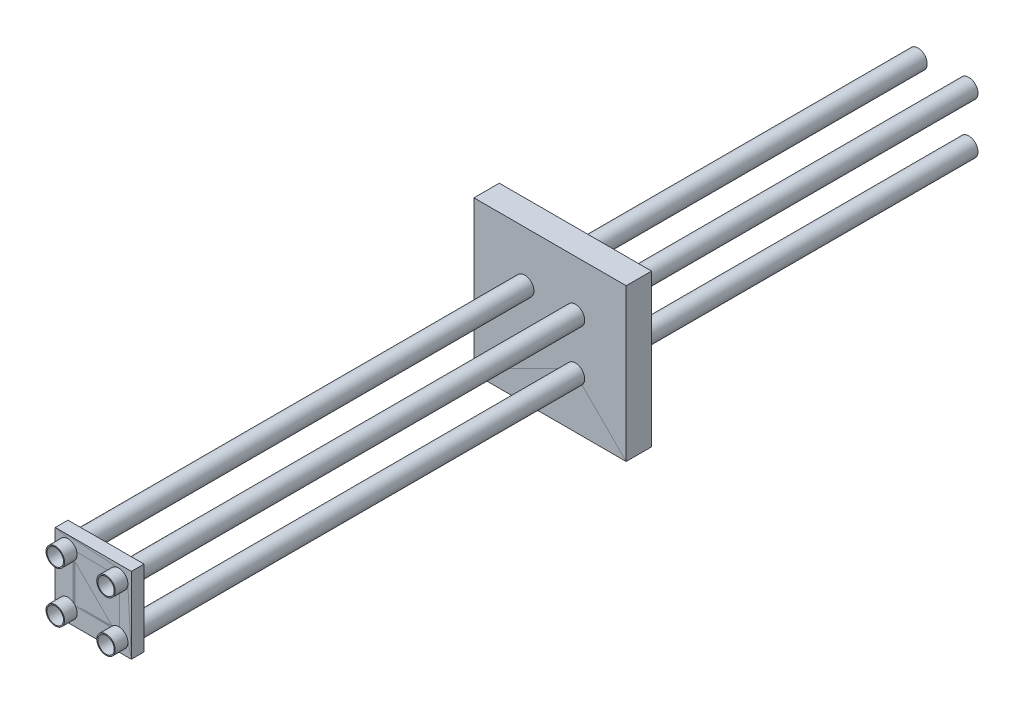
SolidWorks part; units mm, degrees
note: The reader was unsure of these and kept them because the rebuilt part matched: shared geometry of "Sketch7<2>".
ref_plane "Front Plane" through (0, 0, 0) normal (0, 0, 1) x (1, 0, 0)
ref_plane "Top Plane" through (0, 0, 0) normal (0, 1, 0) x (1, 0, 0)
ref_plane "Right Plane" through (0, 0, 0) normal (1, 0, 0) x (0, 0, -1)
sketch "Sketch1" plane through (0, 0, 0) normal (0, 0, 1) x (1, 0, 0)
  line L1 (-1500, 1500) -> (1500, 1500)
  line L2 (-1500, 1500) -> (-1500, -1500)
  line L3 (-1500, -1500) -> (1500, -1500)
  line L4 (1500, 1500) -> (1500, -1500)
  line L5 (-1500, 1500) -> (1500, -1500) construction
  line L6 (-1500, -1500) -> (1500, 1500) construction
  point P0 (0, 0)
  dimension "D1" = 3000
  dimension "D2" = 3000
extrude "Boss-Extrude1" add sketch "Sketch1" along normal blind 500
surface "Surface-Plane1"
shell "Shell1" thickness 10
sketch "Sketch6" plane through (0, 0, 0) normal (0, 0, 1) x (1, 0, 0)
  circle A0 centre (-1000, 1000) radius 325
  dimension "D1" = 650
  dimension "D2" = 1000
  dimension "D3" = 1000
extrude "Extrude-Thin4" add sketch "Sketch6" along normal blind 1000 and the other way blind 33000 thin thin type one direction wall 40
pattern_linear "LPattern1" count 2 spacing 2000 along (1, 0, 0) count 2 spacing 2000 along (0, -1, 0) of "Extrude-Thin4"
ref_plane "Plane1" through (0, 0, -17500) normal (0, 0, 1) x (1, 0, 0)
sketch "Sketch7" plane through (0, 0, -17500) normal (0, 0, 1) x (1, 0, 0)
  line L1 (-3000, 3000) -> (3000, 3000)
  line L2 (-3000, 3000) -> (-3000, -3000)
  line L3 (-3000, -3000) -> (3000, -3000)
  line L4 (3000, 3000) -> (3000, -3000)
  line L5 (-3000, 3000) -> (3000, -3000) construction
  line L6 (-3000, -3000) -> (3000, 3000) construction
  point P0 (0, 0)
  dimension "D1" = 6000
  dimension "D2" = 6000
surface "Surface-Plane2" sketch "Sketch7"
extrude "Boss-Extrude3" add sketch "Sketch7<2>" against normal blind 1000
sketch "Sketch7<2>" plane through (0, 0, -17500) normal (0, 0, 1) x (1, 0, 0) same geometry as "Sketch7"
